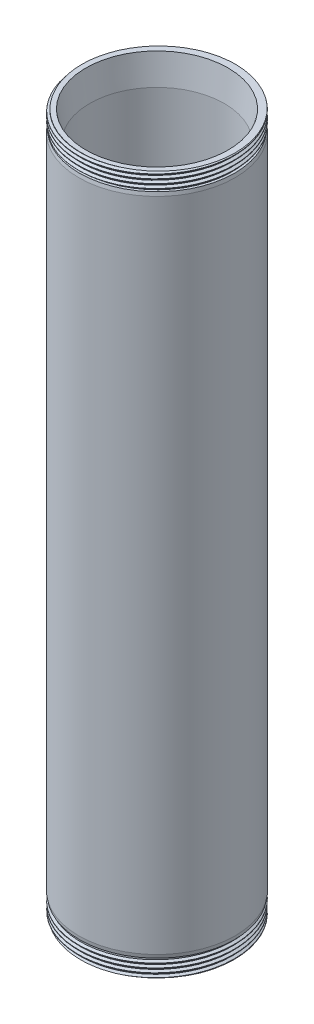
SolidWorks part; units mm, degrees
ref_plane "Plan de face" through (0, 0, 0) normal (0, 0, 1) x (1, 0, 0)
ref_plane "Plan de dessus" through (0, 0, 0) normal (0, 1, 0) x (1, 0, 0)
ref_plane "Plan de droite" through (0, 0, 0) normal (1, 0, 0) x (0, 0, -1)
sketch "Esquisse1" plane through (0, 0, 0) normal (0, 0, 1) x (1, 0, 0)
  line L0 (56, 266) -> (59.1597, 290)
  line L1 (59.1597, 290) -> (65, 290) construction
  line L2 (65, 290) -> (65, -290) construction
  line L4 (59.1597, -290) -> (56, -266)
  line L5 (56, -266) -> (56, 266)
  line L6 (0, 0) -> (0, 367.8577) construction
  line L7 (0, 0) -> (448.2194, 0) construction
  line L9 (65, 273) -> (62, 273) construction
  line L10 (62, 273) -> (62, 267) construction
  line L11 (62, 267) -> (65, 267) construction
  line L12 (65, 267) -> (65, -267)
  line L16 (65, -290) -> (65, -273) construction
  line L17 (59.1597, -290) -> (65, -290) construction
  line L18 (59.1597, 290) -> (63, 290)
  line L19 (63, 290) -> (63, 276) construction
  line L20 (63, 276) -> (64.5, 276)
  line L21 (64.5, 276) -> (65, 273)
  line L22 (64.5, -276) -> (65, -273)
  line L23 (63, -276) -> (64.5, -276)
  line L24 (63, -290) -> (63, -276)
  line L25 (59.1597, -290) -> (63, -290)
  line L26 (63, 290) -> (63, 278)
  line L27 (63, 278) -> (62.5, 278)
  line L28 (62.5, 278) -> (62.5, 276)
  line L29 (62.5, 276) -> (63, 276)
  line L30 (65, 273) -> (65, 267)
  line L31 (65, -273) -> (65, -267)
  point P16 (65, 0)
  dimension "D1" = 532
  dimension "D2" = 580
  dimension "D3" = 56
  dimension "D4" = 65
  dimension "D5" = 580
  dimension "D6" = 7.5
  dimension "D7" = 17
  dimension "D8" = 3
  dimension "D9" = 63
  dimension "D10" = 1.5
  dimension "D11" = 14
  dimension "D12" = 6
  dimension "D13" = 0.5
  dimension "D14" = 2
  dimension "D15" = 65
  dimension "D16" = 9
  dimension "D17" = 56
  dimension "D18" = 3.0414
revolve "Révolution1" add sketch "Esquisse1" angle 360 about L6
thread "Filetage1" pitch 3.5 start angle 0, offset 4, length 20, pitch 3.5, diameter 126
ref_plane "Plan1" through (63, 274, 0) normal (0, 0, 1) x (1, 0, 0)
sketch "Profil de filetage1" plane through (63, 274, 0) normal (0, 0, 1) x (1, 0, 0)
  line L0 (0, 0) -> (0, 3.5) construction
  line L1 (0, 0) -> (1.8944, 1.0937)
  line L2 (1.8944, 1.0937) -> (1.8944, 1.5312)
  line L3 (1.8944, 1.5312) -> (0, 2.625)
  line L4 (1.8944, 1.3125) -> (0, 1.3125) construction
  line L11 (0, 0) -> (0, 2.625)
  point P2 (0, 0)
  dimension "Pitch" = 3.5
  dimension "Profile_Angle" = 60
  dimension "Profile_Land" = 0.4375
  dimension "Profile_Height" = 1.8944
thread "Filetage2" pitch 3.5 profile "Profil de filetage2" start angle 0, offset 0, length 20, pitch 3.5, diameter 126
ref_plane "Plan2" through (-63, -276, 0) normal (0, 0, 1) x (-1, 0, 0)
sketch "Profil de filetage2" plane through (-63, -276, 0) normal (0, 0, 1) x (-1, 0, 0)
  line L0 (0, 0) -> (0, 3.5) construction
  line L1 (0, 0) -> (1.8944, 1.0937)
  line L2 (1.8944, 1.0937) -> (1.8944, 1.5312)
  line L3 (1.8944, 1.5312) -> (0, 2.625)
  line L4 (1.8944, 1.3125) -> (0, 1.3125) construction
  line L11 (0, 0) -> (0, 2.625)
  point P2 (0, 0)
  dimension "Pitch" = 3.5
  dimension "Profile_Angle" = 60
  dimension "Profile_Land" = 0.4375
  dimension "Profile_Height" = 1.8944
